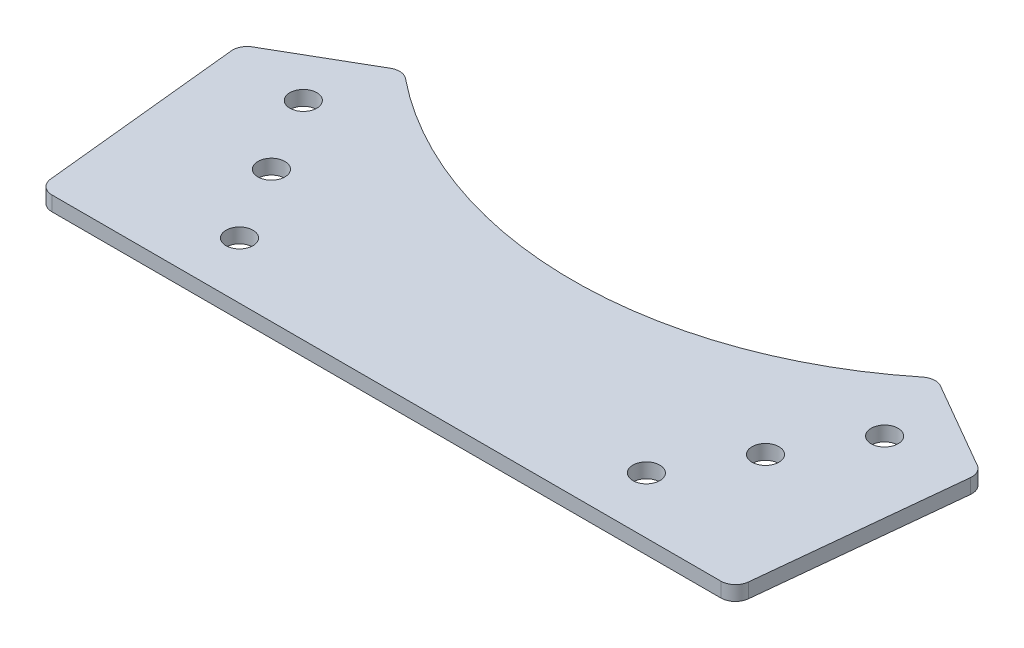
SolidWorks part; units mm, degrees
material "FR4_stuffedProtoboard"
ref_plane "Front Plane" through (0, 0, 0) normal (0, 0, 1) x (1, 0, 0)
ref_plane "Top Plane" through (0, 0, 0) normal (0, 1, 0) x (1, 0, 0)
ref_plane "Right Plane" through (0, 0, 0) normal (1, 0, 0) x (0, 0, -1)
sketch "Sketch1" plane through (0, 0, 0) normal (0, 1, 0) x (1, 0, 0)
  line L0 (-38.1, 9.525) -> (38.1, -9.525) construction
  line L1 (-38.1, 9.525) -> (38.1, 9.525)
  line L2 (-38.1, 9.525) -> (-38.1, -9.525)
  line L3 (-38.1, -9.525) -> (38.1, -9.525)
  line L4 (38.1, 9.525) -> (38.1, -9.525)
  point P4 (0, 0)
  dimension "D1" = 19.05
  dimension "D2" = 76.2
extrude "Boss-Extrude1" add sketch "Sketch1" along normal blind 1.6
sketch "Sketch2" plane through (0, 0, 0) normal (0, -1, 0) x (1, 0, 0)
  line L0 (0, 43.3118) -> (-53.8944, -50.0361) construction
  line L1 (0, -0.88) -> (0, 0.88) construction
  line L2 (-38.1, 9.525) -> (38.1, 9.525) construction
  line L3 (-40.4812, -13.6494) -> (-29.0892, -20.2266)
  line L4 (-29.0892, -20.2266) -> (-22.9106, -9.525)
  line L5 (-22.9106, -9.525) -> (-34.3027, -2.9478)
  line L6 (-34.3027, -2.9478) -> (-40.4812, -13.6494)
  line L7 (38.1, -9.525) -> (-38.1, -9.525) construction
  point P2 (-34.7852, -16.938)
  dimension "D1" = 33.7868
  dimension "D2" = 30
  dimension "D3" = 4.7625
extrude "Boss-Extrude2" add sketch "Sketch2" against normal up to surface (1.6 mm away) up to face at (0, 1.6, 0)
sketch "Sketch3" plane through (0, 0, 0) normal (0, -1, 0) x (1, 0, 0)
  line L0 (-38.1, 9.525) -> (-40.4812, -13.6494)
  line L1 (-40.4812, -13.6494) -> (-22.9106, -9.525)
  line L2 (-22.9106, -9.525) -> (-38.1, 9.525)
extrude "Boss-Extrude3" add sketch "Sketch3" against normal up to surface (1.6 mm away) up to face at (-13.2116, 1.6, -6.2002)
mirror "Mirror1" about plane through (0, 0, 0) normal (1, 0, 0) of "Boss-Extrude3", "Boss-Extrude2"
sketch "Sketch4" plane through (0, 0, 0) normal (0, -1, 0) x (1, 0, 0)
  line L0 (-29.0892, -20.2266) -> (-29.0892, 9.525)
  line L1 (-38.1, 9.525) -> (38.1, 9.525) construction
  line L2 (-29.0892, 9.525) -> (29.0892, 9.525)
  line L3 (29.0892, 9.525) -> (29.0892, -20.2266)
  arc A0 (-29.0892, -20.2266) -> (29.0892, -20.2266) centre (0, -54.5605) cw
  dimension "D1" = 45
extrude "Boss-Extrude4" add sketch "Sketch4" against normal up to surface (1.6 mm away) up to face at (0, 1.6, -8.469)
sketch "Sketch5" plane through (0, 0, 0) normal (0, -1, 0) x (1, 0, 0)
  line L0 (-38.1, 9.525) -> (-37.9695, 10.795)
  line L1 (-37.9695, 10.795) -> (37.9695, 10.795)
  line L2 (37.9695, 10.795) -> (38.1, 9.525)
  line L3 (-38.1, 9.525) -> (-40.4812, -13.6494) construction
  line L4 (38.1, 9.525) -> (40.4812, -13.6494) construction
  line L5 (-38.1, 9.525) -> (38.1, 9.525) construction
  line L6 (-38.1, 9.525) -> (38.1, 9.525)
  dimension "D1" = 1.27
extrude "Boss-Extrude5" add sketch "Sketch5" against normal up to surface (1.6 mm away) up to face at (0, 1.6, -6.3393)
fillet "Fillet4" radius 1.5875 6 edges at (40.4812, 0.8, -13.6494) (37.9695, 0.8, 10.795) (-40.4812, 0.8, -13.6494) (-29.0892, 0.8, -20.2266) (29.0892, 0.8, -20.2266) (-37.9695, 0.8, 10.795)
sketch "Sketch6" plane through (0, 0, 0) normal (0, -1, 0) x (1, 0, 0)
  line L0 (0, -0.88) -> (0, 0.88) construction
  line L1 (36.5368, 10.795) -> (-36.5368, 10.795) construction
  point P10 (-22.225, 4.6217)
  point P11 (-26.9875, -3.6272)
  point P12 (-31.75, -11.8761)
  dimension "D1" = 22.225
  dimension "D2" = 26.9875
  dimension "D3" = 31.75
  dimension "D4" = 6.1733
  dimension "D5" = 14.4222
  dimension "D6" = 22.6711
hole_wizard "#4 Clearance Hole1" positions "3DSketch1" profile "Sketch7" hole size "#4" standard "ANSI Inch" end condition through all
sketch3d "3DSketch1"
  point P0 (-22.225, 0, 4.6217)
  point P3 (-26.9875, 0, -3.6272)
  point P6 (-31.75, 0, -11.8761)
sketch "Sketch7" plane through (-22.225, 0, 4.6217) normal (1, 0, 0) x (0, 0, -1)
  line L0 (0, 0) -> (0, 1.6)
  line L1 (0, 1.6) -> (1.4732, 1.6)
  line L2 (1.4732, 1.6) -> (1.4732, 0)
  line L5 (1.4732, 0) -> (0, 0)
  line L11 (0, -6.35) -> (0, 107.95) construction
  dimension "Thru Hole Dia." = 2.9464
  dimension "Thru Hole Depth" = 1.6
mirror "Mirror2" about plane through (0, 0, 0) normal (1, 0, 0) of "#4 Clearance Hole1"
